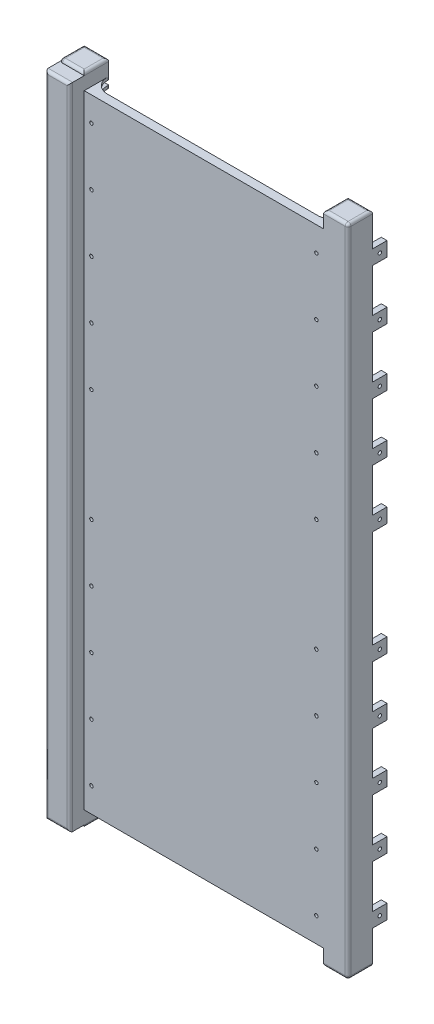
SolidWorks part; units mm, degrees
ref_plane "Front Plane" through (0, 0, 0) normal (0, 0, 1) x (1, 0, 0)
ref_plane "Top Plane" through (0, 0, 0) normal (0, 1, 0) x (1, 0, 0)
ref_plane "Right Plane" through (0, 0, 0) normal (1, 0, 0) x (0, 0, -1)
sketch "Sketch1" plane through (0, 0, 0) normal (0, 1, 0) x (1, 0, 0)
  line L1 (-3.25, -4.25) -> (4.25, -4.25)
  line L2 (-4.25, -3.25) -> (-4.25, 4.25)
  line L3 (-4.25, 4.25) -> (4.25, 4.25)
  line L4 (4.25, -4.25) -> (4.25, 4.25)
  line L5 (-4.25, -4.25) -> (4.25, 4.25) construction
  line L6 (-4.25, 4.25) -> (4.25, -4.25) construction
  arc A0 (-3.25, -4.25) -> (-4.25, -3.25) centre (-3.25, -3.25) cw
  point P0 (0, 0)
  dimension "D2" = 1
  dimension "D1" = 8.5
extrude "Boss-Extrude1" add sketch "Sketch1" along normal blind 227
ref_plane "Plane2" through (45.75, 0, 0) normal (-1, 0, 0) x (0, 0, 1)
ref_plane "Plane3" through (0, 113.5, 0) normal (0, 1, 0) x (1, 0, 0)
fillet "Fillet1" radius 1 10 edges at (0, 0, -4.25) (-4.25, 0, -0.5) (-3.9571, 0, 3.9571) (0.5, 0, 4.25) (4.25, 0, 0) (0.5, 227, 4.25) (-3.9571, 227, 3.9571) (-4.25, 227, -0.5) (0, 227, -4.25) (4.25, 227, 0)
ref_plane "Plane1" through (0, 0, 0) normal (-0.7071, 0, -0.7071) x (-0.7071, 0, 0.7071)
sketch "Sketch2" plane through (4.25, 0, 0) normal (1, 0, 0) x (0, 0, -1)
  line L0 (-4.25, 226) -> (-4.25, 1) construction
  line L1 (-4.25, 215.5) -> (-2.25, 215.5)
  line L2 (-4.25, 215.5) -> (-4.25, 210.5)
  line L3 (-4.25, 210.5) -> (-2.25, 210.5)
  line L4 (-2.25, 215.5) -> (-2.25, 210.5)
  line L5 (-3.25, 227) -> (3.25, 227) construction
  line L6 (-4.25, 195.5) -> (-2.25, 195.5)
  line L8 (-4.25, 195.5) -> (-4.25, 190.5)
  line L9 (-4.25, 190.5) -> (-2.25, 190.5)
  line L10 (-2.25, 195.5) -> (-2.25, 190.5)
  line L11 (-4.25, 175.5) -> (-2.25, 175.5)
  line L12 (-4.25, 175.5) -> (-4.25, 170.5)
  line L13 (-4.25, 170.5) -> (-2.25, 170.5)
  line L14 (-2.25, 175.5) -> (-2.25, 170.5)
  line L15 (-4.25, 155.5) -> (-2.25, 155.5)
  line L16 (-4.25, 155.5) -> (-4.25, 150.5)
  line L17 (-4.25, 150.5) -> (-2.25, 150.5)
  line L18 (-2.25, 155.5) -> (-2.25, 150.5)
  line L19 (-4.25, 135.5) -> (-2.25, 135.5)
  line L20 (-4.25, 135.5) -> (-4.25, 130.5)
  line L21 (-4.25, 130.5) -> (-2.25, 130.5)
  line L22 (-2.25, 135.5) -> (-2.25, 130.5)
  line L27 (-4.25, 120.5) -> (4.25, 120.5) construction
  line L28 (4.25, 226) -> (4.25, 1) construction
  line L29 (-4.25, 220.5) -> (4.25, 220.5) construction
  line L30 (-4.25, 113.5) -> (4.25, 113.5) construction
  line L35 (-2.25, 91.5) -> (-2.25, 96.5)
  line L36 (-4.25, 96.5) -> (-2.25, 96.5)
  line L37 (-4.25, 91.5) -> (-4.25, 96.5)
  line L38 (-4.25, 91.5) -> (-2.25, 91.5)
  line L39 (-2.25, 71.5) -> (-2.25, 76.5)
  line L40 (-4.25, 76.5) -> (-2.25, 76.5)
  line L41 (-4.25, 71.5) -> (-4.25, 76.5)
  line L42 (-4.25, 71.5) -> (-2.25, 71.5)
  line L43 (-2.25, 51.5) -> (-2.25, 56.5)
  line L44 (-4.25, 56.5) -> (-2.25, 56.5)
  line L45 (-4.25, 51.5) -> (-4.25, 56.5)
  line L46 (-4.25, 51.5) -> (-2.25, 51.5)
  line L47 (-2.25, 31.5) -> (-2.25, 36.5)
  line L48 (-4.25, 36.5) -> (-2.25, 36.5)
  line L49 (-4.25, 31.5) -> (-4.25, 36.5)
  line L50 (-4.25, 31.5) -> (-2.25, 31.5)
  line L51 (-2.25, 11.5) -> (-2.25, 16.5)
  line L52 (-4.25, 16.5) -> (-2.25, 16.5)
  line L53 (-4.25, 11.5) -> (-4.25, 16.5)
  line L54 (-4.25, 11.5) -> (-2.25, 11.5)
  line L55 (-4.25, 115.5) -> (-2.25, 115.5) [skipped]
  line L56 (-4.25, 115.5) -> (-4.25, 110.5) [skipped]
  line L57 (-2.25, 115.5) -> (-2.25, 110.5) [skipped]
  line L58 (-4.25, 110.5) -> (-2.25, 110.5) [skipped]
  dimension "D1" = 2
  dimension "D2" = 100
  dimension "D3" = 5
  dimension "D4" = 6
  dimension "D5" = 20
  dimension "D6" = 6.5
  dimension "D7" = 5
extrude "Boss-Extrude2" add sketch "Sketch2" along normal blind 5
sketch "Sketch13" plane through (4.25, 0, 0) normal (-1, 0, 0) x (0, 0, 1)
  line L1 (4.25, 220.5) -> (4.05, 220.5)
  line L2 (4.25, 220.5) -> (4.25, 6.5)
  line L3 (4.25, 6.5) -> (4.05, 6.5)
  line L4 (4.05, 220.5) -> (4.05, 6.5)
  line L6 (3.25, 227) -> (-3.25, 227) construction
  line L7 (-3.25, 0) -> (3.25, 0) construction
  dimension "D1" = 0.2
  dimension "D2" = 6.5
  dimension "D3" = 6.5
extrude "Boss-Extrude6" add sketch "Sketch13" along normal up to surface (41.5 mm away)
hole_wizard "#0-80 Tapped Hole1" positions "Sketch12" profile "Sketch11" tap size "#0-80" standard "ANSI Inch"
sketch "Sketch12" plane through (0, 0, 4.25) normal (0, 0, 1) x (1, 0, 0)
  line L0 (9.25, 215.5) -> (4.25, 215.5) construction
  line L2 (9.25, 215.5) -> (9.25, 210.5) construction
  line L5 (4.25, 113.5) -> (-3.25, 113.5) construction
  line L7 (-3.25, 226) -> (-3.25, 1) construction
  line L8 (4.25, 130.5) -> (4.25, 96.5) construction
  point P0 (6.75, 213)
  point P23 (6.75, 193)
  point P24 (6.75, 173)
  point P25 (6.75, 153)
  point P26 (6.75, 133)
  point P40 (6.75, 94)
  point P41 (6.75, 74)
  point P42 (6.75, 54)
  point P43 (6.75, 34)
  point P44 (6.75, 14)
  dimension "D1" = 2.5
  dimension "D2" = 2.5
  dimension "D4" = 20
  dimension "D3" = 5
sketch "Sketch11" plane through (6.75, 213, 4.25) normal (1, 0, 0) x (0, -1, 0)
  line L0 (0, 0) -> (0, 4.3584)
  line L1 (0, 4.3584) -> (0.5956, 4.0005)
  line L2 (0.5956, 4.0005) -> (0.5956, 0)
  line L5 (0.5956, 0) -> (0, 0)
  line L10 (0, 4.3584) -> (-0.5956, 4.0005) construction
  line L11 (0, -6.35) -> (0, 107.95) construction
  dimension "Tap Drill Dia." = 1.1913
  dimension "Tap Drill Depth" = 4.0005
  dimension "Drill Angle" = 118
cosmetic thread "Hole Thread1" parameters "D1"=2, "D2"=1.524
cosmetic thread "Hole Thread2" parameters "D1"=2, "D2"=1.524
cosmetic thread "Hole Thread11" parameters "D1"=2, "D2"=1.524
cosmetic thread "Hole Thread12" parameters "D1"=2, "D2"=1.524
cosmetic thread "Hole Thread13" parameters "D1"=2, "D2"=1.524
cosmetic thread "Hole Thread14" parameters "D1"=2, "D2"=1.524
cosmetic thread "Hole Thread15" parameters "D1"=2, "D2"=1.524
cosmetic thread "Hole Thread16" parameters "D1"=2, "D2"=1.524
cosmetic thread "Hole Thread17" parameters "D1"=2, "D2"=1.524
cosmetic thread "Hole Thread18" parameters "D1"=2, "D2"=1.524
fillet "Fillet2" radius 2.5 20 edges at (9.25, 215.5, 3.15) (9.25, 195.5, 3.15) (9.25, 175.5, 3.15) (9.25, 155.5, 3.15) (9.25, 135.5, 3.15) (9.25, 91.5, 3.15) (9.25, 71.5, 3.15) (9.25, 51.5, 3.15) (9.25, 31.5, 3.15) (9.25, 11.5, 3.15) (4.25, 215.5, 3.15) (4.25, 195.5, 3.15) (4.25, 175.5, 3.15) (4.25, 155.5, 3.15) (4.25, 135.5, 3.15) (4.25, 91.5, 3.15) (4.25, 71.5, 3.15) (4.25, 51.5, 3.15) (4.25, 11.5, 3.15) (4.25, 31.5, 3.15)
mirror "Mirror1" about plane through (0, 0, 0) normal (-0.7071, 0, -0.7071) of "#0-80 Tapped Hole1", "Boss-Extrude2"
sketch "Sketch3" plane through (0, 227, 0) normal (0, 1, 0) x (1, 0, 0)
  line L1 (-2.25, -2.25) -> (4.25, -2.25)
  line L2 (-2.25, -2.25) -> (-2.25, 4.25)
  line L3 (-2.25, 4.25) -> (4.25, 4.25)
  line L4 (4.25, -2.25) -> (4.25, 4.25)
  line L6 (4.25, -4.25) -> (-3.25, -4.25) construction
  line L7 (-4.25, -3.25) -> (-4.25, 4.25) construction
  dimension "D1" = 2
  dimension "D2" = 2
extrude "Cut-Extrude1" cut sketch "Sketch3" against normal offset from surface (214 mm away) 6.5 from offset 6.5 up to face at (0, 0, 0) offset against normal yes
mirror "Mirror7" about plane through (45.75, 0, 0) normal (-1, 0, 0) of "Fillet2", "Boss-Extrude1", "Fillet1", "Boss-Extrude2", "Boss-Extrude6", "#0-80 Tapped Hole1", "Mirror1", "Cut-Extrude1"
sketch "Sketch14" plane through (-2.25, 0, 0) normal (1, 0, 0) x (0, 0, -1)
  line L0 (-2.25, 6.5) -> (-2.25, 220.5) construction
  line L1 (-4.25, 8.05) -> (4.25, 8.05)
  line L2 (-4.25, 8.05) -> (-4.25, 9.05)
  line L3 (-4.25, 9.05) -> (4.25, 9.05)
  line L4 (4.25, 8.05) -> (4.25, 9.05)
  line L5 (4.25, 6.5) -> (4.25, 11.5) construction
  line L6 (4.25, 6.5) -> (-2.25, 6.5) construction
  line L7 (-4.25, 18.05) -> (4.25, 18.05)
  line L8 (-4.25, 6.5) -> (4.25, 6.5)
  line L9 (-4.25, 6.5) -> (-4.25, 5.5)
  line L10 (-4.25, 5.5) -> (4.25, 5.5)
  line L11 (4.25, 6.5) -> (4.25, 5.5)
  line L12 (-4.25, 18.05) -> (-4.25, 19.05)
  line L13 (-4.25, 19.05) -> (4.25, 19.05)
  line L14 (4.25, 18.05) -> (4.25, 19.05)
  line L15 (-4.25, 16.5) -> (4.25, 16.5)
  line L16 (-4.25, 16.5) -> (-4.25, 15.5)
  line L17 (-4.25, 15.5) -> (4.25, 15.5)
  line L18 (4.25, 16.5) -> (4.25, 15.5)
  line L19 (-4.25, 28.05) -> (4.25, 28.05)
  line L20 (-4.25, 28.05) -> (-4.25, 29.05)
  line L21 (-4.25, 29.05) -> (4.25, 29.05)
  line L22 (4.25, 28.05) -> (4.25, 29.05)
  line L23 (-4.25, 26.5) -> (4.25, 26.5)
  line L24 (-4.25, 26.5) -> (-4.25, 25.5)
  line L25 (-4.25, 25.5) -> (4.25, 25.5)
  line L26 (4.25, 26.5) -> (4.25, 25.5)
  line L27 (-4.25, 38.05) -> (4.25, 38.05)
  line L28 (-4.25, 38.05) -> (-4.25, 39.05)
  line L29 (-4.25, 39.05) -> (4.25, 39.05)
  line L30 (4.25, 38.05) -> (4.25, 39.05)
  line L31 (-4.25, 36.5) -> (4.25, 36.5)
  line L32 (-4.25, 36.5) -> (-4.25, 35.5)
  line L33 (-4.25, 35.5) -> (4.25, 35.5)
  line L34 (4.25, 36.5) -> (4.25, 35.5)
  line L35 (-4.25, 48.05) -> (4.25, 48.05)
  line L36 (-4.25, 48.05) -> (-4.25, 49.05)
  line L37 (-4.25, 49.05) -> (4.25, 49.05)
  line L38 (4.25, 48.05) -> (4.25, 49.05)
  line L39 (-4.25, 46.5) -> (4.25, 46.5)
  line L40 (-4.25, 46.5) -> (-4.25, 45.5)
  line L41 (-4.25, 45.5) -> (4.25, 45.5)
  line L42 (4.25, 46.5) -> (4.25, 45.5)
  line L43 (-4.25, 58.05) -> (4.25, 58.05)
  line L44 (-4.25, 58.05) -> (-4.25, 59.05)
  line L45 (-4.25, 59.05) -> (4.25, 59.05)
  line L46 (4.25, 58.05) -> (4.25, 59.05)
  line L47 (-4.25, 56.5) -> (4.25, 56.5)
  line L48 (-4.25, 56.5) -> (-4.25, 55.5)
  line L49 (-4.25, 55.5) -> (4.25, 55.5)
  line L50 (4.25, 56.5) -> (4.25, 55.5)
  line L51 (-4.25, 68.05) -> (4.25, 68.05)
  line L52 (-4.25, 68.05) -> (-4.25, 69.05)
  line L53 (-4.25, 69.05) -> (4.25, 69.05)
  line L54 (4.25, 68.05) -> (4.25, 69.05)
  line L55 (-4.25, 66.5) -> (4.25, 66.5)
  line L56 (-4.25, 66.5) -> (-4.25, 65.5)
  line L57 (-4.25, 65.5) -> (4.25, 65.5)
  line L58 (4.25, 66.5) -> (4.25, 65.5)
  line L59 (-4.25, 78.05) -> (4.25, 78.05)
  line L60 (-4.25, 78.05) -> (-4.25, 79.05)
  line L61 (-4.25, 79.05) -> (4.25, 79.05)
  line L62 (4.25, 78.05) -> (4.25, 79.05)
  line L63 (-4.25, 76.5) -> (4.25, 76.5)
  line L64 (-4.25, 76.5) -> (-4.25, 75.5)
  line L65 (-4.25, 75.5) -> (4.25, 75.5)
  line L66 (4.25, 76.5) -> (4.25, 75.5)
  line L67 (-4.25, 88.05) -> (4.25, 88.05)
  line L68 (-4.25, 88.05) -> (-4.25, 89.05)
  line L69 (-4.25, 89.05) -> (4.25, 89.05)
  line L70 (4.25, 88.05) -> (4.25, 89.05)
  line L71 (-4.25, 86.5) -> (4.25, 86.5)
  line L72 (-4.25, 86.5) -> (-4.25, 85.5)
  line L73 (-4.25, 85.5) -> (4.25, 85.5)
  line L74 (4.25, 86.5) -> (4.25, 85.5)
  line L75 (-4.25, 98.05) -> (4.25, 98.05)
  line L76 (-4.25, 98.05) -> (-4.25, 99.05)
  line L77 (-4.25, 99.05) -> (4.25, 99.05)
  line L78 (4.25, 98.05) -> (4.25, 99.05)
  line L79 (-4.25, 96.5) -> (4.25, 96.5)
  line L80 (-4.25, 96.5) -> (-4.25, 95.5)
  line L81 (-4.25, 95.5) -> (4.25, 95.5)
  line L82 (4.25, 96.5) -> (4.25, 95.5)
  line L83 (-4.25, 108.05) -> (4.25, 108.05)
  line L84 (-4.25, 108.05) -> (-4.25, 109.05)
  line L85 (-4.25, 109.05) -> (4.25, 109.05)
  line L86 (4.25, 108.05) -> (4.25, 109.05)
  line L87 (-4.25, 106.5) -> (4.25, 106.5)
  line L88 (-4.25, 106.5) -> (-4.25, 105.5)
  line L89 (-4.25, 105.5) -> (4.25, 105.5)
  line L90 (4.25, 106.5) -> (4.25, 105.5)
  line L91 (4.25, 96.5) -> (4.25, 130.5) construction
  line L92 (4.25, 113.5) -> (-2.25, 113.5) construction
  line L93 (4.25, 120.5) -> (4.25, 121.5)
  line L94 (-4.25, 121.5) -> (4.25, 121.5)
  line L95 (-4.25, 120.5) -> (-4.25, 121.5)
  line L96 (-4.25, 120.5) -> (4.25, 120.5)
  line L97 (4.25, 118.95) -> (4.25, 117.95)
  line L98 (-4.25, 117.95) -> (4.25, 117.95)
  line L99 (-4.25, 118.95) -> (-4.25, 117.95)
  line L100 (-4.25, 118.95) -> (4.25, 118.95)
  line L101 (4.25, 130.5) -> (4.25, 131.5)
  line L102 (-4.25, 131.5) -> (4.25, 131.5)
  line L103 (-4.25, 130.5) -> (-4.25, 131.5)
  line L104 (-4.25, 130.5) -> (4.25, 130.5)
  line L105 (4.25, 128.95) -> (4.25, 127.95)
  line L106 (-4.25, 127.95) -> (4.25, 127.95)
  line L107 (-4.25, 128.95) -> (-4.25, 127.95)
  line L108 (-4.25, 128.95) -> (4.25, 128.95)
  line L109 (4.25, 140.5) -> (4.25, 141.5)
  line L110 (-4.25, 141.5) -> (4.25, 141.5)
  line L111 (-4.25, 140.5) -> (-4.25, 141.5)
  line L112 (-4.25, 140.5) -> (4.25, 140.5)
  line L113 (4.25, 138.95) -> (4.25, 137.95)
  line L114 (-4.25, 137.95) -> (4.25, 137.95)
  line L115 (-4.25, 138.95) -> (-4.25, 137.95)
  line L116 (-4.25, 138.95) -> (4.25, 138.95)
  line L117 (4.25, 150.5) -> (4.25, 151.5)
  line L118 (-4.25, 151.5) -> (4.25, 151.5)
  line L119 (-4.25, 150.5) -> (-4.25, 151.5)
  line L120 (-4.25, 150.5) -> (4.25, 150.5)
  line L121 (4.25, 148.95) -> (4.25, 147.95)
  line L122 (-4.25, 147.95) -> (4.25, 147.95)
  line L123 (-4.25, 148.95) -> (-4.25, 147.95)
  line L124 (-4.25, 148.95) -> (4.25, 148.95)
  line L125 (4.25, 160.5) -> (4.25, 161.5)
  line L126 (-4.25, 161.5) -> (4.25, 161.5)
  line L127 (-4.25, 160.5) -> (-4.25, 161.5)
  line L128 (-4.25, 160.5) -> (4.25, 160.5)
  line L129 (4.25, 158.95) -> (4.25, 157.95)
  line L130 (-4.25, 157.95) -> (4.25, 157.95)
  line L131 (-4.25, 158.95) -> (-4.25, 157.95)
  line L132 (-4.25, 158.95) -> (4.25, 158.95)
  line L133 (4.25, 170.5) -> (4.25, 171.5)
  line L134 (-4.25, 171.5) -> (4.25, 171.5)
  line L135 (-4.25, 170.5) -> (-4.25, 171.5)
  line L136 (-4.25, 170.5) -> (4.25, 170.5)
  line L137 (4.25, 168.95) -> (4.25, 167.95)
  line L138 (-4.25, 167.95) -> (4.25, 167.95)
  line L139 (-4.25, 168.95) -> (-4.25, 167.95)
  line L140 (-4.25, 168.95) -> (4.25, 168.95)
  line L141 (4.25, 180.5) -> (4.25, 181.5)
  line L142 (-4.25, 181.5) -> (4.25, 181.5)
  line L143 (-4.25, 180.5) -> (-4.25, 181.5)
  line L144 (-4.25, 180.5) -> (4.25, 180.5)
  line L145 (4.25, 178.95) -> (4.25, 177.95)
  line L146 (-4.25, 177.95) -> (4.25, 177.95)
  line L147 (-4.25, 178.95) -> (-4.25, 177.95)
  line L148 (-4.25, 178.95) -> (4.25, 178.95)
  line L149 (4.25, 190.5) -> (4.25, 191.5)
  line L150 (-4.25, 191.5) -> (4.25, 191.5)
  line L151 (-4.25, 190.5) -> (-4.25, 191.5)
  line L152 (-4.25, 190.5) -> (4.25, 190.5)
  line L153 (4.25, 188.95) -> (4.25, 187.95)
  line L154 (-4.25, 187.95) -> (4.25, 187.95)
  line L155 (-4.25, 188.95) -> (-4.25, 187.95)
  line L156 (-4.25, 188.95) -> (4.25, 188.95)
  line L157 (4.25, 200.5) -> (4.25, 201.5)
  line L158 (-4.25, 201.5) -> (4.25, 201.5)
  line L159 (-4.25, 200.5) -> (-4.25, 201.5)
  line L160 (-4.25, 200.5) -> (4.25, 200.5)
  line L161 (4.25, 198.95) -> (4.25, 197.95)
  line L162 (-4.25, 197.95) -> (4.25, 197.95)
  line L163 (-4.25, 198.95) -> (-4.25, 197.95)
  line L164 (-4.25, 198.95) -> (4.25, 198.95)
  line L165 (4.25, 210.5) -> (4.25, 211.5)
  line L166 (-4.25, 211.5) -> (4.25, 211.5)
  line L167 (-4.25, 210.5) -> (-4.25, 211.5)
  line L168 (-4.25, 210.5) -> (4.25, 210.5)
  line L169 (4.25, 208.95) -> (4.25, 207.95)
  line L170 (-4.25, 207.95) -> (4.25, 207.95)
  line L171 (-4.25, 208.95) -> (-4.25, 207.95)
  line L172 (4.25, 220.5) -> (4.25, 221.5)
  line L173 (-4.25, 221.5) -> (4.25, 221.5)
  line L174 (-4.25, 220.5) -> (-4.25, 221.5)
  line L175 (-4.25, 220.5) -> (4.25, 220.5)
  line L176 (-4.25, 208.95) -> (4.25, 208.95)
  line L177 (4.25, 218.95) -> (4.25, 217.95)
  line L178 (-4.25, 217.95) -> (4.25, 217.95)
  line L179 (-4.25, 218.95) -> (-4.25, 217.95)
  line L180 (-4.25, 218.95) -> (4.25, 218.95)
  dimension "D1" = 1
  dimension "D2" = 1.55
  dimension "D4" = 10
  dimension "D5" = 8.5
  dimension "D3" = 11
extrude "Boss-Extrude7" add sketch "Sketch14" along normal up to surface (96 mm away)
sketch "Sketch15" plane through (0, 5.5, 0) normal (0, -1, 0) x (1, 0, 0)
  line L0 (4.25, -4.25) -> (4.25, -3.75)
  line L2 (4.25, -4.25) -> (87.25, -4.25)
  line L3 (87.25, -4.25) -> (87.25, -3.75)
  line L4 (87.25, -4.25) -> (87.25, 4.25) construction
  line L5 (4.25, 4.25) -> (4.25, -4.25) construction
  line L6 (9.25, 1.25) -> (82.25, 1.25)
  line L7 (87.25, 4.25) -> (4.25, 4.25) construction
  arc A0 (4.25, -3.75) -> (9.25, 1.25) centre (9.25, -3.75) cw
  arc A1 (87.25, -3.75) -> (82.25, 1.25) centre (82.25, -3.75) ccw
  point P14 (4.25, 1.25)
  point P17 (87.25, 1.25)
  dimension "D2" = 5
  dimension "D1" = 3
extrude "Cut-Extrude2" cut sketch "Sketch15" against normal through all
sketch "Sketch17" plane through (0, 0, 4.25) normal (0, 0, 1) x (1, 0, 0)
  line L1 (-4.25, 226) -> (4.25, 226)
  line L2 (-4.25, 226) -> (-4.25, 1)
  line L3 (-4.25, 1) -> (4.25, 1)
  line L4 (4.25, 226) -> (4.25, 1)
extrude "Boss-Extrude8" add sketch "Sketch17" along normal blind 5 and the other way blind 1
sketch "Sketch16" plane through (87.25, 0, 0) normal (-1, 0, 0) x (0, 0, 1)
  line L0 (4.05, 218.95) -> (2.25, 218.95) construction
  line L1 (4.05, 220.5) -> (-10.95, 220.5)
  line L2 (4.05, 220.5) -> (4.05, 218.95)
  line L3 (4.05, 218.95) -> (-10.95, 218.95)
  line L4 (-10.95, 220.5) -> (-10.95, 218.95)
  line L5 (4.05, 210.5) -> (-10.95, 210.5)
  line L6 (4.05, 210.5) -> (4.05, 208.95)
  line L7 (4.05, 208.95) -> (-10.95, 208.95)
  line L8 (-10.95, 210.5) -> (-10.95, 208.95)
  line L9 (4.05, 200.5) -> (-10.95, 200.5)
  line L10 (4.05, 200.5) -> (4.05, 198.95)
  line L11 (4.05, 198.95) -> (-10.95, 198.95)
  line L12 (-10.95, 200.5) -> (-10.95, 198.95)
  line L13 (4.05, 190.5) -> (-10.95, 190.5)
  line L14 (4.05, 190.5) -> (4.05, 188.95)
  line L15 (4.05, 188.95) -> (-10.95, 188.95)
  line L16 (-10.95, 190.5) -> (-10.95, 188.95)
  line L17 (4.05, 180.5) -> (-10.95, 180.5)
  line L18 (4.05, 180.5) -> (4.05, 178.95)
  line L19 (4.05, 178.95) -> (-10.95, 178.95)
  line L20 (-10.95, 180.5) -> (-10.95, 178.95)
  line L21 (4.05, 170.5) -> (-10.95, 170.5)
  line L22 (4.05, 170.5) -> (4.05, 168.95)
  line L23 (4.05, 168.95) -> (-10.95, 168.95)
  line L24 (-10.95, 170.5) -> (-10.95, 168.95)
  line L25 (4.05, 160.5) -> (-10.95, 160.5)
  line L26 (4.05, 160.5) -> (4.05, 158.95)
  line L27 (4.05, 158.95) -> (-10.95, 158.95)
  line L28 (-10.95, 160.5) -> (-10.95, 158.95)
  line L29 (4.05, 150.5) -> (-10.95, 150.5)
  line L30 (4.05, 150.5) -> (4.05, 148.95)
  line L31 (4.05, 148.95) -> (-10.95, 148.95)
  line L32 (-10.95, 150.5) -> (-10.95, 148.95)
  line L33 (4.05, 140.5) -> (-10.95, 140.5)
  line L34 (4.05, 140.5) -> (4.05, 138.95)
  line L35 (4.05, 138.95) -> (-10.95, 138.95)
  line L36 (-10.95, 140.5) -> (-10.95, 138.95)
  line L37 (4.05, 130.5) -> (-10.95, 130.5)
  line L38 (4.05, 130.5) -> (4.05, 128.95)
  line L39 (4.05, 128.95) -> (-10.95, 128.95)
  line L40 (-10.95, 130.5) -> (-10.95, 128.95)
  line L41 (4.05, 120.5) -> (-10.95, 120.5)
  line L42 (4.05, 120.5) -> (4.05, 118.95)
  line L43 (4.05, 118.95) -> (-10.95, 118.95)
  line L44 (-10.95, 120.5) -> (-10.95, 118.95)
  line L46 (2.25, 113.5) -> (-20.3315, 113.5) construction
  line L47 (2.25, 109.05) -> (2.25, 117.95) construction
  line L48 (-10.95, 106.5) -> (-10.95, 108.05)
  line L49 (4.05, 108.05) -> (-10.95, 108.05)
  line L50 (4.05, 106.5) -> (4.05, 108.05)
  line L51 (4.05, 106.5) -> (-10.95, 106.5)
  line L52 (-10.95, 96.5) -> (-10.95, 98.05)
  line L53 (4.05, 98.05) -> (-10.95, 98.05)
  line L54 (4.05, 96.5) -> (4.05, 98.05)
  line L55 (4.05, 96.5) -> (-10.95, 96.5)
  line L56 (-10.95, 86.5) -> (-10.95, 88.05)
  line L57 (4.05, 88.05) -> (-10.95, 88.05)
  line L58 (4.05, 86.5) -> (4.05, 88.05)
  line L59 (4.05, 86.5) -> (-10.95, 86.5)
  line L60 (-10.95, 76.5) -> (-10.95, 78.05)
  line L61 (4.05, 78.05) -> (-10.95, 78.05)
  line L62 (4.05, 76.5) -> (4.05, 78.05)
  line L63 (4.05, 76.5) -> (-10.95, 76.5)
  line L64 (-10.95, 66.5) -> (-10.95, 68.05)
  line L65 (4.05, 68.05) -> (-10.95, 68.05)
  line L66 (4.05, 66.5) -> (4.05, 68.05)
  line L67 (4.05, 66.5) -> (-10.95, 66.5)
  line L68 (-10.95, 56.5) -> (-10.95, 58.05)
  line L69 (4.05, 58.05) -> (-10.95, 58.05)
  line L70 (4.05, 56.5) -> (4.05, 58.05)
  line L71 (4.05, 56.5) -> (-10.95, 56.5)
  line L72 (-10.95, 46.5) -> (-10.95, 48.05)
  line L73 (4.05, 48.05) -> (-10.95, 48.05)
  line L74 (4.05, 46.5) -> (4.05, 48.05)
  line L75 (4.05, 46.5) -> (-10.95, 46.5)
  line L76 (-10.95, 36.5) -> (-10.95, 38.05)
  line L77 (4.05, 38.05) -> (-10.95, 38.05)
  line L78 (4.05, 36.5) -> (4.05, 38.05)
  line L79 (4.05, 36.5) -> (-10.95, 36.5)
  line L80 (-10.95, 26.5) -> (-10.95, 28.05)
  line L81 (4.05, 28.05) -> (-10.95, 28.05)
  line L82 (4.05, 26.5) -> (4.05, 28.05)
  line L83 (4.05, 26.5) -> (-10.95, 26.5)
  line L84 (-10.95, 16.5) -> (-10.95, 18.05)
  line L85 (4.05, 18.05) -> (-10.95, 18.05)
  line L86 (4.05, 16.5) -> (4.05, 18.05)
  line L87 (4.05, 16.5) -> (-10.95, 16.5)
  line L88 (-10.95, 6.5) -> (-10.95, 8.05)
  line L89 (4.05, 8.05) -> (-10.95, 8.05)
  line L90 (4.05, 6.5) -> (4.05, 8.05)
  line L91 (4.05, 6.5) -> (-10.95, 6.5)
  dimension "D1" = 15
  dimension "D3" = 10
  dimension "D2" = 11
extrude "Cut-Extrude3" cut sketch "Sketch16" along normal through all
fillet "Fillet3" radius 1 4 edges at (0, 1, 9.25) (0, 226, 9.25) (4.25, 113.5, 9.25) (-4.25, 113.5, 9.25)
